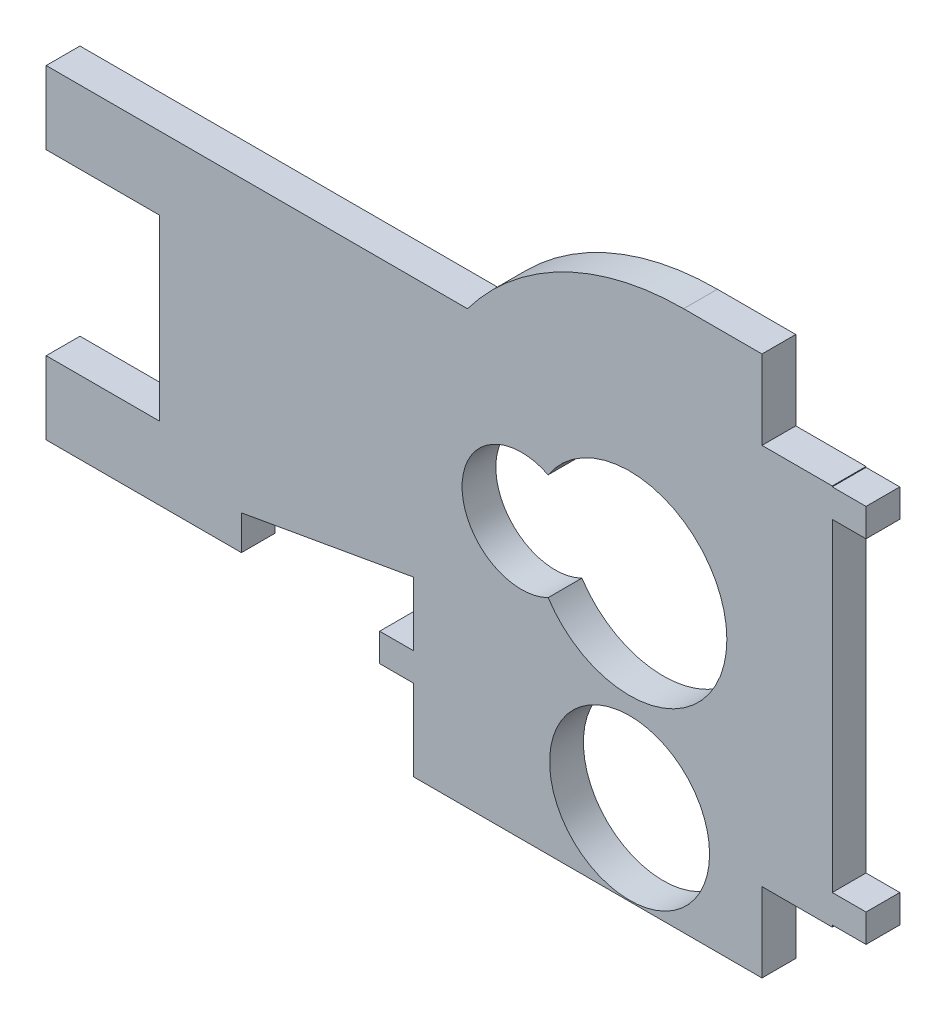
SolidWorks part; units mm, degrees
material "Balsa"
ref_plane "Front Plane" through (0, 0, 0) normal (0, 0, 1) x (1, 0, 0)
ref_plane "Top Plane" through (0, 0, 0) normal (0, 1, 0) x (1, 0, 0)
ref_plane "Right Plane" through (0, 0, 0) normal (1, 0, 0) x (0, 0, -1)
sketch "Sketch1" plane through (0, 0, 0) normal (0, 0, 1) x (1, 0, 0)
  line L0 (0, -1000.1535) -> (0, 48999.8465) construction
  line L1 (0, 9.144) -> (-5.08, 9.144) construction
  line L2 (-1000, 0) -> (49000, 0) construction
  line L3 (9.525, 16.51) -> (11.1125, 16.51)
  line L4 (2.54, 21.59) -> (9.525, 21.59)
  line L5 (-10.16, 8.89) -> (-10.16, -3.81)
  line L6 (-10.16, -3.81) -> (9.525, -3.81)
  line L7 (9.525, 21.59) -> (9.525, -3.81)
  line L8 (-11.7475, 0) -> (-10.16, 0)
  line L9 (-11.7475, 0) -> (-11.7475, 1.3208)
  line L10 (-11.7475, 1.3208) -> (-10.16, 1.3208)
  line L11 (-10.16, 0) -> (-10.16, 1.3208)
  line L12 (9.525, 0) -> (11.1125, 0)
  line L13 (9.525, 0) -> (9.525, 1.3208)
  line L14 (9.525, 1.3208) -> (11.1125, 1.3208)
  line L15 (11.1125, 0) -> (11.1125, 1.3208)
  line L16 (9.525, 16.51) -> (9.525, 17.8308)
  line L17 (9.525, 17.8308) -> (11.1125, 17.8308)
  line L18 (11.1125, 16.51) -> (11.1125, 17.8308)
  line L19 (-7.62, 16.51) -> (-27.4189, 16.51)
  line L20 (-27.4189, 16.51) -> (-27.4189, 1.27)
  line L21 (-27.4189, 1.27) -> (-10.16, 4.318)
  line L22 (9.525, 8.89) -> (-35.5862, 8.89) construction
  line L23 (-27.4189, 1.27) -> (-18.2418, 1.27)
  line L24 (-27.4189, 13.081) -> (-22.0849, 13.081)
  line L25 (-27.4189, 13.081) -> (-27.4189, 4.699)
  line L26 (-27.4189, 4.699) -> (-22.0849, 4.699)
  line L27 (-22.0849, 13.081) -> (-22.0849, 4.699)
  line L28 (-18.2418, 1.27) -> (-18.2418, 2.8907)
  circle A0 centre (0, 0) radius 3.7592
  arc A1 (-3.829, 6.6457) -> (-3.829, 11.6423) centre (0, 9.144) ccw
  arc A2 (-3.829, 11.6423) -> (-3.829, 6.6457) centre (-5.08, 9.144) ccw
  arc A3 (2.54, 21.59) -> (-10.16, 8.89) centre (2.54, 8.89) ccw
  point P33 (9.525, 8.89)
  point P35 (-27.4189, 8.89)
  point P41 (-27.4189, 8.89)
  dimension "D1" = 7.5184
  dimension "D4" = 3.81
  dimension "D3" = 9.144
  dimension "D5" = 2.794
  dimension "D9" = 12.7
  dimension "D10" = 1.5875
  dimension "D2" = 25.4
  dimension "D6" = 9.525
  dimension "D7" = 5.08
  dimension "D8" = 19.685
  dimension "D11" = 9.144
  dimension "D12" = 1.3208
  dimension "D13" = 1.3208
  dimension "D14" = 1.5875
  dimension "D15" = 2
  dimension "D16" = 8.128
  dimension "D17" = 15.24
  dimension "D18" = 17.526
  dimension "D19" = 8.382
  dimension "D20" = 5.334
extrude "Boss-Extrude1" add sketch "Sketch1" along normal blind 1.5875 contours L4 A3 L5 L6 L7 A0 A2 A1 | L10 L9 L8 L5 | L3 L18 L17 L7 | L12 L15 L14 L7 | A3 L19 L20 L21 L5 | L23 L28 L21 region at (10.3187, 17.1704, 0) region at (9.2036, 8.9154, 0) region at (10.3187, 0.6604, 0) region at (-17.5342, 9.9456, 0) region at (-10.9538, 0.6604, 0) region at (-21.3008, 1.8102, 0)
sketch "Sketch2" plane through (0, 0, 1.5875) normal (0, 0, 1) x (1, 0, 0)
  line L0 (9.525, -0.9144) -> (9.525, -3.0226) construction
  line L1 (6.223, -3.8481) -> (9.525, -3.8481)
  line L2 (6.223, -3.8481) -> (6.223, -0.0889)
  line L3 (6.223, -0.0889) -> (9.525, -0.0889)
  line L4 (9.525, -3.8481) -> (9.525, -0.0889)
  line L5 (9.525, -0.9144) -> (9.525, -3.0226)
  line L6 (9.525, 20.8026) -> (9.525, 18.6944) construction
  line L7 (9.525, 20.8026) -> (9.525, 18.6944)
  line L9 (6.223, 17.8689) -> (9.525, 17.8689)
  line L10 (6.223, 17.8689) -> (6.223, 21.6281)
  line L11 (6.223, 21.6281) -> (9.525, 21.6281)
  line L12 (9.525, 17.8689) -> (9.525, 21.6281)
  point P8 (9.525, -1.9685)
  point P9 (9.525, -1.9685)
  point P10 (9.525, 19.7485)
  point P15 (9.525, 19.7485)
  line M4 (9.525, 21.59) -> (2.54, 21.59)
  line M11 (-10.16, -3.81) -> (9.525, -3.81)
  line M12 (9.525, -3.81) -> (9.525, 0)
  line M20 (9.525, 17.8308) -> (9.525, 21.59)
  dimension "D1" = 3.7592
  dimension "D2" = 3.302
  dimension "D3" = 3.7592
  dimension "D4" = 3.302
extrude "Cut-Extrude1" cut sketch "Sketch2" against normal up to next contours L3 L2 L4 M11 M12 | L10 L9 M20 M4 region at (7.874, -1.9495, 1.5875) region at (7.874, 19.7294, 1.5875)
